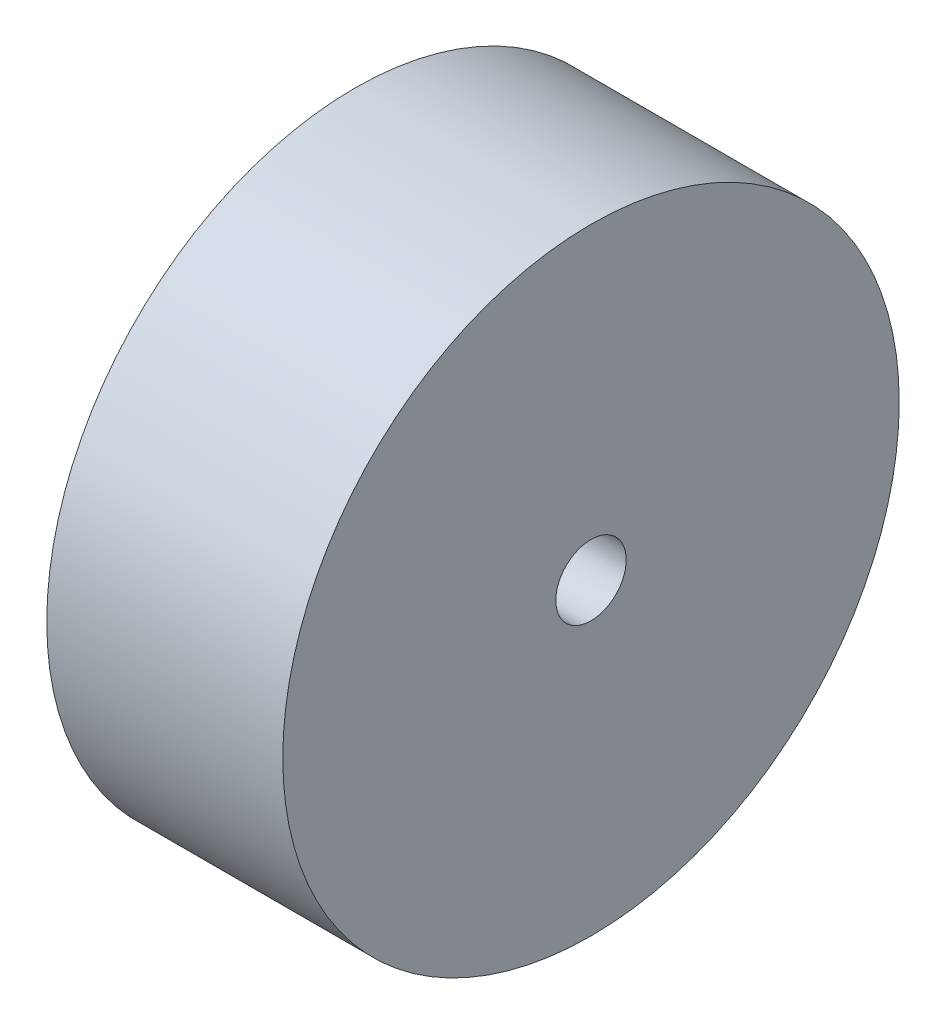
SolidWorks part; units mm, degrees
ref_plane "Front Plane" through (0, 0, 0) normal (0, 0, 1) x (1, 0, 0)
ref_plane "Top Plane" through (0, 0, 0) normal (0, 1, 0) x (1, 0, 0)
ref_plane "Right Plane" through (0, 0, 0) normal (1, 0, 0) x (0, 0, -1)
sketch "Sketch1" plane through (0, 0, 0) normal (1, 0, 0) x (0, 0, -1)
  circle A0 centre (0, 0) radius 17.5
  dimension "D1" = 35
extrude "Boss-Extrude1" add sketch "Sketch1" along normal blind 6.7 and the other way blind 6.7
sketch "Sketch2" plane through (6.7, 0, 0) normal (1, 0, 0) x (0, 0, -1)
  circle A0 centre (0, 0) radius 2
  dimension "D1" = 4
extrude "Cut-Extrude1" cut sketch "Sketch2" against normal through all
equation "\"wheel diam\"= 35mm"
equation "\"wheel_hole\"= 4mm"
equation "\"wheel_depth\"= 13.4mm"
equation "\"D1@Sketch1\"= \"wheel diam\""
equation "\"D1@Sketch2\"= \"wheel_hole\""
